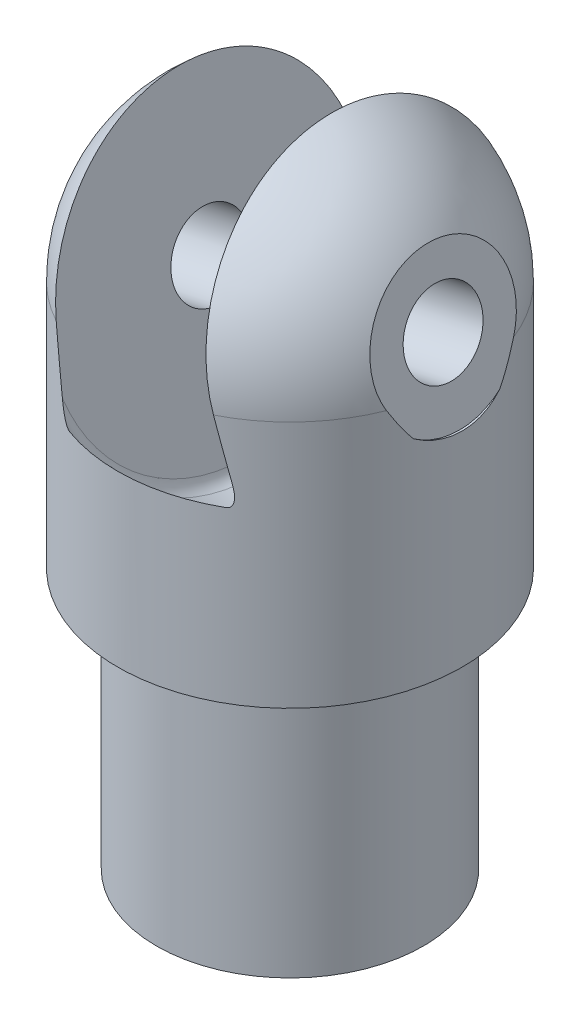
SolidWorks part; units mm, degrees
ref_plane "Front Plane" through (0, 0, 0) normal (0, 0, 1) x (1, 0, 0)
ref_plane "Top Plane" through (0, 0, 0) normal (0, 1, 0) x (1, 0, 0)
ref_plane "Right Plane" through (0, 0, 0) normal (1, 0, 0) x (0, 0, -1)
sketch "Sketch1" plane through (0, 0, 0) normal (0, 1, 0) x (1, 0, 0)
  circle A0 centre (0, 0) radius 12.9921
extrude "Boss-Extrude1" add sketch "Sketch1" along normal blind 25.4 contours A0
sketch "Sketch2" plane through (0, 0, 0) normal (1, 0, 0) x (0, 0, -1)
  line L0 (-16.764, 25.4) -> (-16.764, 49.53)
  line L1 (0, 25.4) -> (-16.764, 25.4)
  line L4 (12.9921, 25.4) -> (-12.9921, 25.4) construction
  line L5 (0, 14.2913) -> (0, -14.2913) construction
  line L6 (0, 25.4) -> (0, 66.294)
  arc A0 (0, 66.294) -> (-16.764, 49.53) centre (0, 49.53) ccw
  dimension "D1" = 33.528
  dimension "D2" = 24.13
revolve "Revolve1" add sketch "Sketch2" angle 360 about L6
ref_plane "Plane2" through (0, 49.53, 0) normal (0, -1, 0) x (-1, 0, 0)
ref_axis "Axis1" through (0, 49.53, 23.7) along (0, 0, -1)
ref_plane "Plane3" through (-10.0728, 47.389, 0) normal (0.2079, -0.9781, 0) x (0, 0, -1)
ref_plane "Plane4" through (10.0728, 2.141, 0) normal (-0.9781, -0.2079, 0) x (0, 0, -1)
sketch "Sketch3" plane through (-10.3665, 98.3003, 0) normal (-0.9781, -0.2079, 0) x (0, 0, -1)
  line L1 (-23.7, 49.8599) -> (13.1808, 49.8599) construction
  line L2 (0, 49.8599) -> (0, 73.4626) construction
  circle A2 centre (0, 49.8599) radius 3.81
  dimension "D1" = 7.62
extrude "Cut-Extrude1" cut sketch "Sketch3" against normal through all both and the other way through all
ref_axis "Axis2" through (17.4875, 53.2471, 0) along (-0.9781, -0.2079, 0)
sketch "Sketch10" plane through (0, 0, 0) normal (0, 0, 1) x (1, 0, 0)
  line L0 (17.4875, 53.2471) -> (-17.6069, 45.7875) construction
  line L1 (-7.7019, 47.8929) -> (7.205, 51.0615)
  point P5 (-0.2484, 49.4772)
  dimension "D1" = 15.24
  dimension "D2" = 0.254
sketch "Sketch11" plane through (0, 0, 0) normal (0, 0, 1) x (1, 0, 0)
  line L2 (-7.7019, 47.8929) -> (7.205, 51.0615) construction
  line L3 (-7.7019, 47.8929) -> (-11.163, 64.1758)
  line L4 (7.205, 51.0615) -> (3.696, 67.5703)
  line L5 (-7.7019, 47.8929) -> (7.205, 51.0615)
  arc A0 (3.696, 67.5703) -> (-11.163, 64.1758) centre (0, 49.53) ccw
  arc A1 (15.1764, 56.651) -> (-16.7607, 49.8625) centre (0, 49.53) ccw construction
  dimension "D1" = 18.415
revolve "Cut-Revolve10" cut sketch "Sketch11" angle 90 about axis through (17.4875, 53.2471, 0) along (-0.9781, -0.2079, 0) other way angle 180
sketch "Sketch13" plane through (0, 0, 0) normal (0, 0, 1) x (1, 0, 0)
  line L0 (-8.4941, 51.6196) -> (6.4129, 54.7882)
  line L1 (-8.0499, 49.53) -> (-10.779, 62.3692) construction
  line L2 (4.0741, 65.7914) -> (7.5306, 49.53) construction
  line L3 (-7.7019, 47.8929) -> (7.205, 51.0615) construction
  line L4 (-8.4941, 51.6196) -> (-11.9796, 68.0178)
  line L5 (6.4129, 54.7882) -> (2.9274, 71.1864)
  arc A0 (2.9274, 71.1864) -> (-11.9796, 68.0178) centre (-1.0406, 53.2039) ccw
  dimension "D1" = 3.81
  dimension "D2" = 36.83
revolve "Cut-Revolve11" cut sketch "Sketch13" angle 360 about L0
sketch "Sketch14" plane through (0, 0, 0) normal (0, 0, 1) x (1, 0, 0)
  line L0 (-7.7019, 47.8929) -> (7.205, 51.0615) construction
  line L1 (-7.7019, 47.8929) -> (-6.1497, 40.59)
  line L2 (7.205, 51.0615) -> (8.7573, 43.7586)
  line L3 (-7.7019, 47.8929) -> (7.205, 51.0615)
  arc A0 (-6.1497, 40.59) -> (8.7573, 43.7586) centre (-0.2484, 49.4772) ccw
  dimension "D1" = 21.336
extrude "Cut-Extrude4" cut sketch "Sketch14" against normal blind 32.004
fillet "Fillet1" radius 1.27 6 edges at (-4.84, 34.4287, 9.3615) (-5.3066, 36.6236, -6.7827) (-6.1497, 40.59, -14.0004) (8.7573, 43.7586, -13.3502) (9.6004, 39.7921, -6.7827) (10.2986, 36.5075, 7.9665)
ref_plane "Plane5" through (-4.8341, -1.0275, 0) normal (-0.9781, -0.2079, 0) x (0, 0, -1)
sketch "Sketch15" plane through (-4.8341, -1.0275, 0) normal (-0.9781, -0.2079, 0) x (0, 0, -1)
  circle A0 centre (0, -48.4477) radius 7.62
  dimension "D1" = 15.24
extrude "Cut-Extrude5" cut sketch "Sketch15" along normal blind 10.16
mirror "Mirror1" about plane through (10.0728, 2.141, 0) normal (-0.9781, -0.2079, 0) of "Cut-Extrude5"
